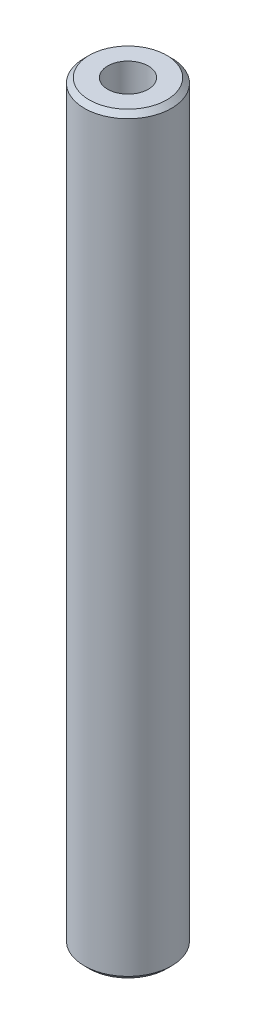
SolidWorks part; units mm, degrees
ref_plane "Front Plane" through (0, 0, 0) normal (0, 0, 1) x (1, 0, 0)
ref_plane "Top Plane" through (0, 0, 0) normal (0, 1, 0) x (1, 0, 0)
ref_plane "Right Plane" through (0, 0, 0) normal (1, 0, 0) x (0, 0, -1)
sketch "Sketch1" plane through (0, 0, 0) normal (0, 1, 0) x (1, 0, 0)
  circle A0 centre (0, 0) radius 10
  dimension "SHAFT_OD" = 20
extrude "Boss-Extrude1" add sketch "Sketch1" along normal blind 172.776
sketch "Sketch2" plane through (0, 0, 0) normal (0, 1, 0) x (1, 0, 0)
  circle A0 centre (0, 0) radius 4.6555
  dimension "BORE_D" = 9.311
extrude "Cut-Extrude1" cut sketch "Sketch2" along normal through all
chamfer "Chamfer1" distance 1.1132 angle 45 2 edges at (0, 172.776, 10) (0, 0, 10)
